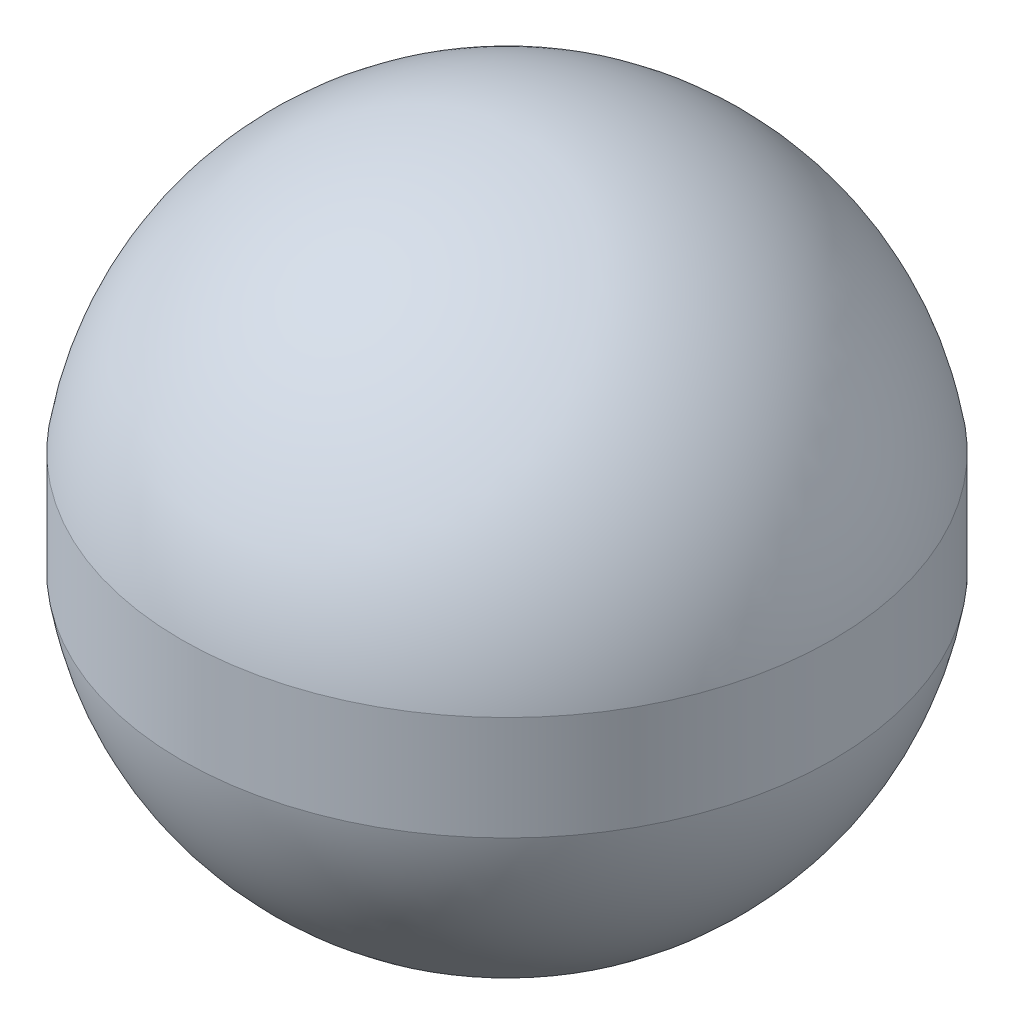
SolidWorks part; units mm, degrees
material "Polyetheretherketone (PEEK)"
ref_plane "Front Plane" through (0, 0, 0) normal (0, 0, 1) x (1, 0, 0)
ref_plane "Top Plane" through (0, 0, 0) normal (0, 1, 0) x (1, 0, 0)
ref_plane "Right Plane" through (0, 0, 0) normal (1, 0, 0) x (0, 0, -1)
sketch "Sketch1" plane through (0, 0, 0) normal (0, 0, 1) x (1, 0, 0)
  line L0 (0, 7.9375) -> (0, -7.9375)
  line L1 (7.8375, 1.256) -> (7.8375, -1.256)
  line L2 (0, -7.9365) -> (0.126, -7.9365)
  arc A0 (0, -7.9375) -> (0, 7.9375) centre (0, 0) ccw
  point P1 (7.9375, 0)
  dimension "D1" = 7.9375
  dimension "D2" = 7.8375
  dimension "D3" = 0.001
revolve "Revolve1" add sketch "Sketch1" angle 360 about L0 region at (3.3611, 0, 0)
sketch "Sketch2" plane through (0, -7.9365, 0) normal (0, -1, 0) x (-1, 0, 0)
  point P0 (0, 0)
sketch "Sketch3" plane through (0, 0, 0) normal (0, 1, 0) x (1, 0, 0)
  point P0 (0, 0)
ref_axis "Axis1" through (0, 0, 0) along (0, -1, 0)
sketch3d "3DSketch1"
  line L1 (0, -7.9365, 0) -> (0, 0, 0) construction
equation "\"D1@Sketch1\"=(0.625in)/2"
equation "\"D2@Sketch1\"=\"D1@Sketch1\"-0.1"
